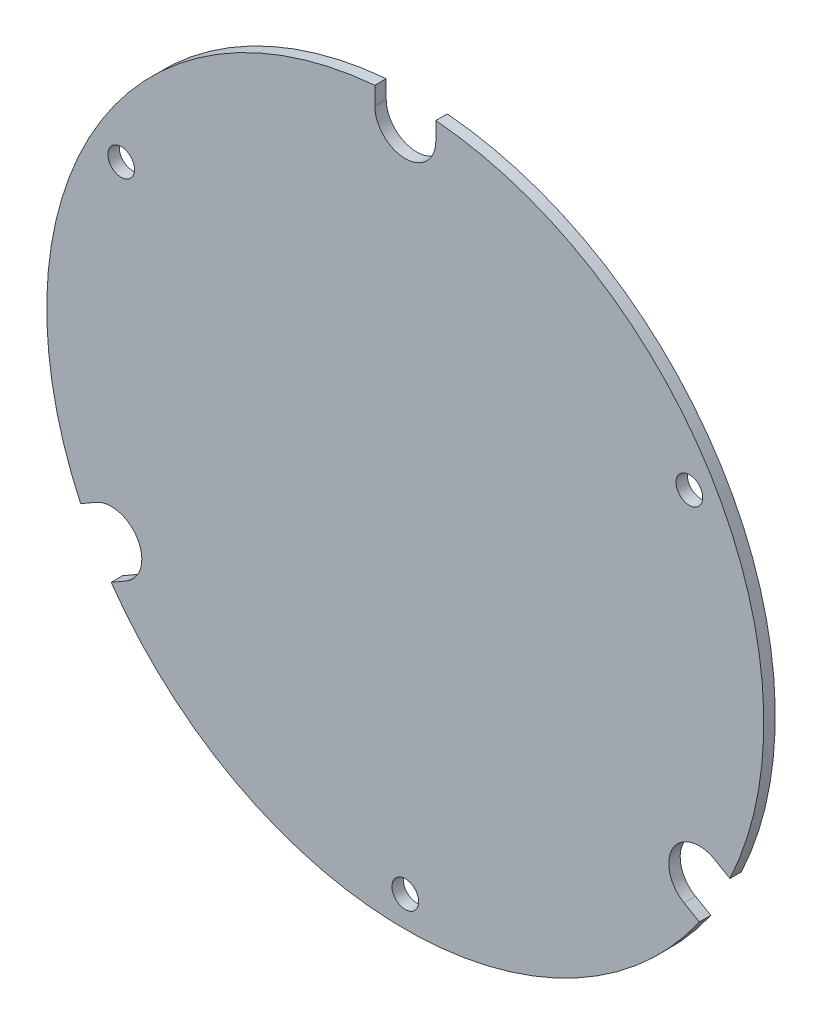
SolidWorks part; units mm, degrees
ref_plane "Alzado" through (0, 0, 0) normal (0, 0, 1) x (1, 0, 0)
ref_plane "Planta" through (0, 0, 0) normal (0, 1, 0) x (1, 0, 0)
ref_plane "Vista lateral" through (0, 0, 0) normal (1, 0, 0) x (0, 0, -1)
sketch "Croquis1" plane through (0, 0, 0) normal (0, 0, 1) x (1, 0, 0)
  line L0 (-3, 44.5) -> (-3, 47.9062) construction
  line L1 (3, 44.5) -> (3, 47.9062) construction
  line L2 (0, 44.5) -> (0, 0) construction
  line L3 (37.0381, -24.8481) -> (39.988, -26.5512) construction
  line L4 (40.0381, -19.6519) -> (42.988, -21.355) construction
  line L5 (-40.0381, -19.6519) -> (-42.988, -21.355) construction
  line L6 (-37.0381, -24.8481) -> (-39.988, -26.5512) construction
  line L7 (0, 0) -> (0, 44.5) construction
  line L8 (0, 0) -> (38.5381, -22.25) construction
  line L9 (-4, 44.5) -> (-4, 46.8295)
  line L10 (-40.5381, -18.7859) -> (-42.5555, -19.9506)
  line L11 (-36.5381, -25.7141) -> (-38.5555, -26.8788)
  line L12 (36.5381, -25.7141) -> (38.5555, -26.8788)
  line L13 (40.5381, -18.7859) -> (42.5555, -19.9506)
  line L14 (4, 44.5) -> (4, 46.8295)
  line L15 (1, 44.5) -> (1, 0)
  arc A0 (-39.988, -26.5512) -> (39.988, -26.5512) centre (0, 0) ccw construction
  arc A1 (-3, 44.5) -> (3, 44.5) centre (0, 44.5) ccw construction
  arc A2 (40.0381, -19.6519) -> (37.0381, -24.8481) centre (38.5381, -22.25) ccw construction
  arc A3 (-37.0381, -24.8481) -> (-40.0381, -19.6519) centre (-38.5381, -22.25) ccw construction
  arc A4 (42.988, -21.355) -> (3, 47.9062) centre (0, 0) ccw construction
  arc A5 (-3, 47.9062) -> (-42.988, -21.355) centre (0, 0) ccw construction
  arc A6 (-4, 46.8295) -> (-42.5555, -19.9506) centre (0, 0) ccw
  arc A7 (-36.5381, -25.7141) -> (-40.5381, -18.7859) centre (-38.5381, -22.25) ccw
  arc A8 (-38.5555, -26.8788) -> (38.5555, -26.8788) centre (0, 0) ccw
  arc A9 (40.5381, -18.7859) -> (36.5381, -25.7141) centre (38.5381, -22.25) ccw
  arc A10 (42.5555, -19.9506) -> (4, 46.8295) centre (0, 0) ccw
  arc A11 (-4, 44.5) -> (4, 44.5) centre (0, 44.5) ccw
  dimension "D1" = 96
  dimension "D2" = 44.5
  dimension "D3" = 6
  dimension "D4" = 3
  dimension "D5" = 120
  dimension "D6" = 1
extrude "Saliente-Extruir1" add sketch "Croquis1" along normal blind 1.5 contours A11 L9 A6 L10 A7 L11 A8 L12 A9 L13 A10 L14 region at (0, 0, 0)
sketch "Croquis2" plane through (0, 0, 1.5) normal (0, 0, 1) x (1, 0, 0)
  line L0 (0, 0) -> (-37.2391, 21.5) construction
  line L1 (0, 0) -> (0, 40.5) construction
  line L2 (0, 0) -> (-37.2391, 21.5) construction
  line L3 (0, 0) -> (37.2391, 21.5) construction
  circle A0 centre (-37.2391, 21.5) radius 1.75
  arc A1 (-4, 44.5) -> (4, 44.5) centre (0, 44.5) ccw construction
  circle A2 centre (37.2391, 21.5) radius 1.75
  circle A3 centre (0, -43) radius 1.75
  dimension "D1" = 3.5
  dimension "D2" = 60
  dimension "D3" = 43
  dimension "D5" = 120
  dimension "D4" = 3
extrude "Cortar-Extruir1" cut sketch "Croquis2" against normal blind 1.5
